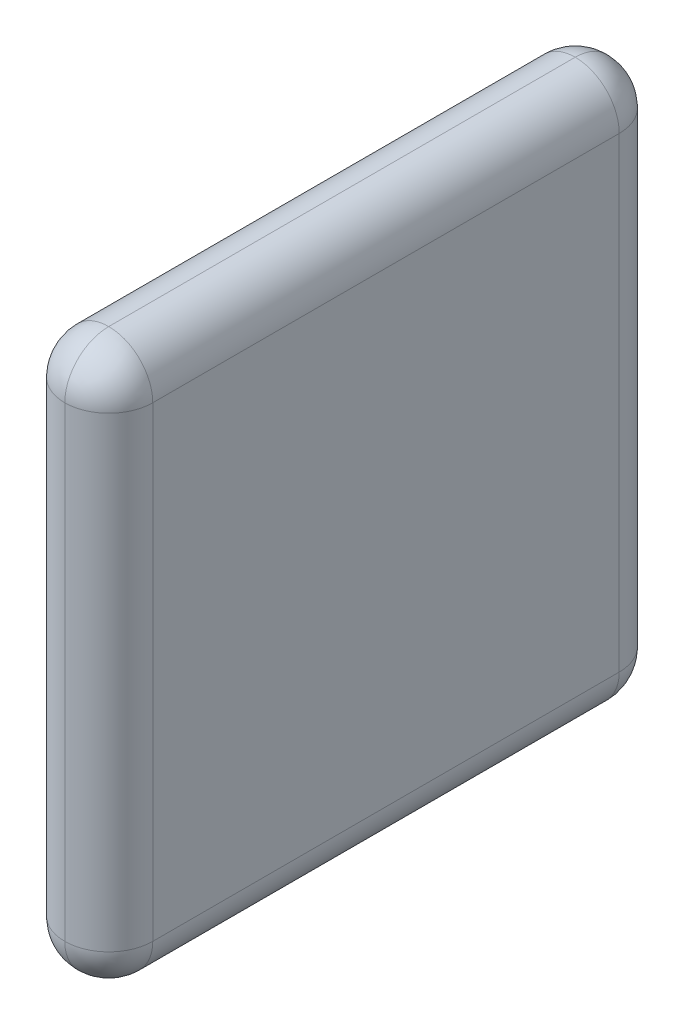
SolidWorks part; units mm, degrees
ref_plane "Front Plane" through (0, 0, 0) normal (0, 0, 1) x (1, 0, 0)
ref_plane "Top Plane" through (0, 0, 0) normal (0, 1, 0) x (1, 0, 0)
ref_plane "Right Plane" through (0, 0, 0) normal (1, 0, 0) x (0, 0, -1)
sketch "Sketch1" plane through (0, 0, 0) normal (1, 0, 0) x (0, 0, -1)
  line L1 (-3.15, -3.15) -> (3.15, -3.15)
  line L2 (-3.15, -3.15) -> (-3.15, 3.15)
  line L3 (-3.15, 3.15) -> (3.15, 3.15)
  line L4 (3.15, -3.15) -> (3.15, 3.15)
  line L5 (-3.15, -3.15) -> (3.15, 3.15) construction
  line L6 (-3.15, 3.15) -> (3.15, -3.15) construction
  point P0 (0, 0)
  dimension "D1" = 6.3
  dimension "D2" = 6.3
extrude "Boss-Extrude1" add sketch "Sketch1" along normal blind 1
fillet "Fillet1" radius 0.5 8 edges at (1, -3.15, 0) (0, -3.15, 0) (1, 0, -3.15) (0, 0, -3.15) (1, 3.15, 0) (0, 3.15, 0) (1, 0, 3.15) (0, 0, 3.15)
